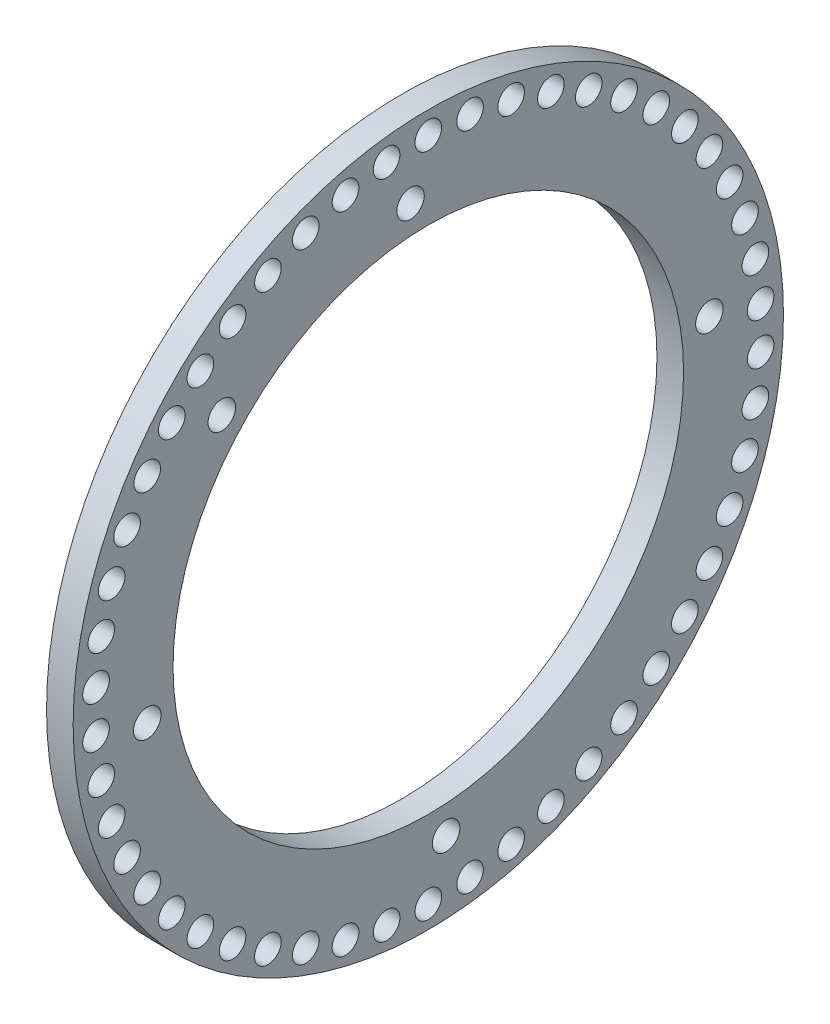
SolidWorks part; units mm, degrees
material "AISI 304"
ref_plane "Front Plane" through (0, 0, 0) normal (0, 0, 1) x (1, 0, 0)
ref_plane "Top Plane" through (0, 0, 0) normal (0, 1, 0) x (1, 0, 0)
ref_plane "Right Plane" through (0, 0, 0) normal (1, 0, 0) x (0, 0, -1)
sketch "Sketch1" plane through (0, 0, 0) normal (1, 0, 0) x (0, 0, -1)
  line L0 (0, 0) -> (0, 40) construction
  line L66 (0, 0) -> (40, 0) construction
  line L67 (0, 0) -> (-40, 0) construction
  line L72 (0, 0) -> (0, -40) construction
  circle A3 centre (0, 0) radius 40
  circle A24 centre (0, 37.5) radius 1.5
  circle A25 centre (0, 0) radius 28.75
  circle A26 centre (4.7, 37.2043) radius 1.5
  circle A27 centre (9.3259, 36.3219) radius 1.5
  circle A28 centre (13.8047, 34.8666) radius 1.5
  circle A29 centre (18.0658, 32.8615) radius 1.5
  circle A30 centre (22.0419, 30.3381) radius 1.5
  circle A31 centre (25.6705, 27.3363) radius 1.5
  circle A32 centre (28.8942, 23.9034) radius 1.5
  circle A33 centre (31.6623, 20.0935) radius 1.5
  circle A34 centre (33.931, 15.9667) radius 1.5
  circle A35 centre (35.6646, 11.5881) radius 1.5
  circle A36 centre (36.8358, 7.0268) radius 1.5
  circle A37 centre (37.426, 2.3546) radius 1.5
  circle A38 centre (37.426, -2.3546) radius 1.5
  circle A39 centre (36.8358, -7.0268) radius 1.5
  circle A40 centre (35.6646, -11.5881) radius 1.5
  circle A41 centre (33.931, -15.9667) radius 1.5
  circle A42 centre (31.6623, -20.0935) radius 1.5
  circle A43 centre (28.8942, -23.9034) radius 1.5
  circle A44 centre (25.6705, -27.3363) radius 1.5
  circle A45 centre (22.0419, -30.3381) radius 1.5
  circle A46 centre (18.0658, -32.8615) radius 1.5
  circle A47 centre (13.8047, -34.8666) radius 1.5
  circle A48 centre (9.3259, -36.3219) radius 1.5
  circle A49 centre (4.7, -37.2043) radius 1.5
  circle A50 centre (0, -37.5) radius 1.5
  circle A51 centre (-4.7, -37.2043) radius 1.5
  circle A52 centre (-9.3259, -36.3219) radius 1.5
  circle A53 centre (-13.8047, -34.8666) radius 1.5
  circle A54 centre (-18.0658, -32.8615) radius 1.5
  circle A55 centre (-22.0419, -30.3381) radius 1.5
  circle A56 centre (-25.6705, -27.3363) radius 1.5
  circle A57 centre (-28.8942, -23.9034) radius 1.5
  circle A58 centre (-31.6623, -20.0935) radius 1.5
  circle A59 centre (-33.931, -15.9667) radius 1.5
  circle A60 centre (-35.6646, -11.5881) radius 1.5
  circle A61 centre (-36.8358, -7.0268) radius 1.5
  circle A62 centre (-37.426, -2.3546) radius 1.5
  circle A63 centre (-37.426, 2.3546) radius 1.5
  circle A64 centre (-36.8358, 7.0268) radius 1.5
  circle A65 centre (-35.6646, 11.5881) radius 1.5
  circle A66 centre (-33.931, 15.9667) radius 1.5
  circle A67 centre (-31.6623, 20.0935) radius 1.5
  circle A68 centre (-28.8942, 23.9034) radius 1.5
  circle A69 centre (-25.6705, 27.3363) radius 1.5
  circle A70 centre (-22.0419, 30.3381) radius 1.5
  circle A71 centre (-18.0658, 32.8615) radius 1.5
  circle A72 centre (-13.8047, 34.8666) radius 1.5
  circle A73 centre (-9.3259, 36.3219) radius 1.5
  circle A74 centre (-4.7, 37.2043) radius 1.5
  circle A75 centre (-2.0035, 31.8444) radius 1.55
  circle A76 centre (-31.6557, -3.999) radius 1.55
  circle A77 centre (2.0035, -31.8444) radius 1.55
  circle A78 centre (31.6557, 3.999) radius 1.55
  circle A79 centre (-23.2594, 21.8421) radius 1.55
  point P9 (0, -20)
  point P11 (-20, 0)
  point P29 (20, 0)
  point P75 (0, 0)
  point P93 (0, 0)
  point P95 (0, 0)
  point P117 (0, 0)
  dimension "D1" = 50
  dimension "D2" = 80
  dimension "D3" = 57.5
  dimension "D5" = 2.5
  dimension "D10" = 6
  dimension "D4" = 3
  dimension "D14" = 3.1
  dimension "D15" = 3.1
  dimension "D16" = 3.1
  dimension "D17" = 3.1
  dimension "D18" = 3.1
  dimension "D6" = 6
  dimension "D7" = 6
  dimension "D8" = 6
  dimension "D9" = 6
  dimension "D12" = 6
  dimension "D13" = 6
  dimension "D11" = 6
  dimension "D19" = 6
  dimension "D20" = 6
extrude "Boss-Extrude4" add sketch "Sketch1" along normal blind 3
